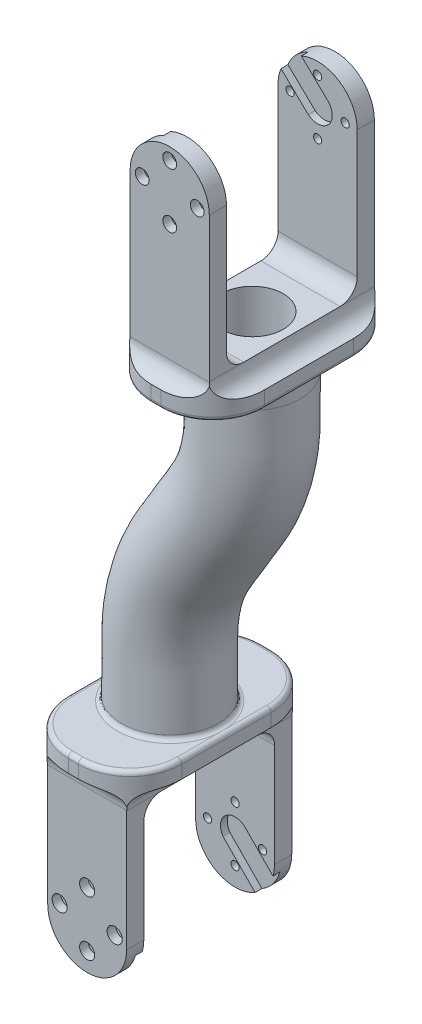
SolidWorks part; units mm, degrees
note: The reader was unsure of these and kept them because the rebuilt part matched: shared geometry of "Croquis37<4>".
material "PLA"
ref_plane "Alzado" through (0, 0, 0) normal (0, 0, 1) x (1, 0, 0)
ref_plane "Planta" through (0, 0, 0) normal (0, 1, 0) x (1, 0, 0)
ref_plane "Vista lateral" through (0, 0, 0) normal (1, 0, 0) x (0, 0, -1)
other "Centro de masa"
sketch "Croquis1" plane through (0, 0, 0) normal (0, 1, 0) x (1, 0, 0)
  circle A0 centre (0, 0) radius 14
  point P0 (0, 0)
  dimension "D1" = 28
extrude "Saliente-Extruir1" add sketch "Croquis1" along normal blind 5
sketch "Croquis2" plane through (0, 5, 0) normal (0, 1, 0) x (1, 0, 0)
  line L1 (16.5, 28) -> (-16.5, 28)
  line L2 (16.5, 28) -> (16.5, -28)
  line L3 (16.5, -28) -> (-16.5, -28)
  line L4 (-16.5, 28) -> (-16.5, -28)
  line L5 (16.5, 28) -> (-16.5, -28) construction
  line L6 (16.5, -28) -> (-16.5, 28) construction
  point P0 (0, 0)
  point P1 (0, 0)
  point P2 (0, 0)
  dimension "D1" = 33
  dimension "D2" = 56
extrude "Saliente-Extruir2" add sketch "Croquis2" along normal blind 5
sketch "Croquis5" plane through (0, 10, 0) normal (0, 1, 0) x (1, 0, 0)
  line L1 (-11.5, 24) -> (11.5, 24)
  line L2 (-11.5, 24) -> (-11.5, -24)
  line L3 (-11.5, -24) -> (11.5, -24)
  line L4 (11.5, 24) -> (11.5, -24)
  line L5 (-11.5, 24) -> (11.5, -24) construction
  line L6 (-11.5, -24) -> (11.5, 24) construction
  point P0 (0, 0)
  dimension "D1" = 48
  dimension "D2" = 23
extrude "Saliente-Extruir5" add sketch "Croquis5" along normal blind 5
sketch "Croquis10" plane through (0, 15, 0) normal (0, 1, 0) x (1, 0, 0)
  line L0 (11.5, -24) -> (11.5, 24) construction
  line L1 (-11.5, 24) -> (11.5, 24)
  line L2 (-11.5, 24) -> (-11.5, 19)
  line L3 (-11.5, 19) -> (11.5, 19)
  line L4 (11.5, 24) -> (11.5, 19)
  dimension "D1" = 5
extrude "Saliente-Extruir9" add sketch "Croquis10" along normal blind 42
sketch "Croquis11" plane through (0, 0, -24) normal (0, 0, -1) x (-1, 0, 0)
  line L0 (-11.5, 57) -> (11.5, 57) construction
  line L1 (-11.5, 57) -> (11.5, 57)
  arc A0 (11.5, 57) -> (-11.5, 57) centre (0, 57) ccw
extrude "Saliente-Extruir10" add sketch "Croquis11" against normal blind 5
sketch "Croquis13" plane through (0, 0, -19) normal (0, 0, 1) x (1, 0, 0)
  line L0 (-9.1006, 57) -> (9.153, 57) construction
  line L1 (0, 65.2781) -> (0, 47.2436) construction
  circle A0 centre (0, 57) radius 8
  circle A1 centre (0, 57) radius 4
  dimension "D1" = 16
  dimension "D2" = 8
hole_wizard "Taladro de margen para M21" positions "Croquis3D1" profile "Croquis15" hole size "M2" standard "ISO" end condition through all
sketch3d "Croquis3D1"
  line L0 (-9.1006, 57, -19) -> (9.153, 57, -19) construction
  line L1 (0, 65.2781, -19) -> (0, 47.2436, -19) construction
  circle A0 centre (0, 57, -19) radius 8 construction
  point P0 (-8, 57, -19)
  point P4 (0, 57, -11)
  point P7 (0, 65, -19)
  point P11 (8, 57, -19)
  point P12 (0, 49, -19)
sketch "Croquis15" plane through (-8, 57, -19) normal (1, 0, 0) x (0, -1, 0)
  line L0 (0, 0) -> (0, 9)
  line L1 (0, 9) -> (1.2, 9)
  line L2 (1.2, 9) -> (1.2, 0)
  line L5 (1.2, 0) -> (0, 0)
  line L11 (0, -6.35) -> (0, 107.95) construction
  dimension "Diámetro de taladro hasta el siguiente" = 2.4
  dimension "Profundidad de taladro hasta el siguiente" = 9
mirror "Simetría2" about plane through (0, 0, 0) normal (0, 0, 1) of "Taladro de margen para M21", "Saliente-Extruir9", "Saliente-Extruir10"
sketch "Croquis35" plane through (0, 0, 24) normal (0, 0, 1) x (1, 0, 0)
  circle A0 centre (0, 49) radius 2
  circle A1 centre (-8, 57) radius 2
  circle A2 centre (0, 65) radius 2
  circle A3 centre (8, 57) radius 2
  dimension "D1" = 4
  dimension "D2" = 4
  dimension "D3" = 4
  dimension "D4" = 4
extrude "Cortar-Extruir2" cut sketch "Croquis35" against normal blind 2.5
sketch "Croquis36" plane through (0, 0, 0) normal (0, -1, 0) x (1, 0, 0)
  circle A0 centre (0, 0) radius 14
  dimension "D1" = 28
sketch "Croquis37" plane through (0, 0, 0) normal (0, 0, 1) x (1, 0, 0)
  line L0 (0, 0) -> (0, -11.1508)
  line L1 (-7.1254, -36.8756) -> (-16.8746, -53.1244)
  line L2 (-24, -78.8492) -> (-24, -95)
  arc A0 (-16.8746, -53.1244) -> (-24, -78.8492) centre (26, -78.8492) ccw
  arc A1 (0, -11.1508) -> (-7.1254, -36.8756) centre (-50, -11.1508) cw
  point P7 (-24, -65)
  point P10 (0, -25)
  dimension "D5" = 50
  dimension "D1" = 25
  dimension "D2" = 30
  dimension "D3" = 24
  dimension "D4" = 95
sweep "Barrer1" add profiles "Croquis36" path "Croquis37"
sketch "Croquis39" plane through (0, -95, 0) normal (0, -1, 0) x (1, 0, 0)
  line L1 (-40.5, 28) -> (-7.5, 28)
  line L2 (-40.5, 28) -> (-40.5, -28)
  line L3 (-40.5, -28) -> (-7.5, -28)
  line L4 (-7.5, 28) -> (-7.5, -28)
  line L5 (-40.5, 28) -> (-7.5, -28) construction
  line L6 (-40.5, -28) -> (-7.5, 28) construction
  circle A1 centre (-24, 0) radius 14
  circle A2 centre (-24, 0) radius 14
  dimension "D2" = 33
  dimension "D3" = 56
  dimension "D1" = 0
extrude "Saliente-Extruir11" add sketch "Croquis39" along normal blind 5 separate body
sketch "Croquis40" plane through (0, -100, 0) normal (0, -1, 0) x (1, 0, 0)
  circle A0 centre (-24, 0) radius 14
  dimension "D1" = 28
extrude "Saliente-Extruir12" add sketch "Croquis40" against normal blind 5
sketch "Croquis42" plane through (0, -100, 0) normal (0, -1, 0) x (1, 0, 0)
  line L0 (-40.5, 0) -> (-7.5, 0) construction
  line L1 (-40.5, 28) -> (-40.5, -28) construction
  line L2 (-7.5, -28) -> (-7.5, 28) construction
  line L3 (-24, 28) -> (-24, -28) construction
  line L4 (-7.5, 28) -> (-40.5, 28) construction
  line L5 (-40.5, -28) -> (-7.5, -28) construction
  line L7 (-35.5, 24) -> (-12.5, 24)
  line L8 (-35.5, 24) -> (-35.5, -24)
  line L9 (-35.5, -24) -> (-12.5, -24)
  line L10 (-12.5, 24) -> (-12.5, -24)
  line L11 (-35.5, 24) -> (-12.5, -24) construction
  line L12 (-35.5, -24) -> (-12.5, 24) construction
  point P12 (-24, 0)
  dimension "D1" = 48
  dimension "D2" = 23
extrude "Saliente-Extruir13" add sketch "Croquis42" along normal blind 5
sketch "Croquis43" plane through (0, -105, 0) normal (0, -1, 0) x (1, 0, 0)
  line L6 (-12.5, -24) -> (-12.5, 24) construction
  line L7 (-35.5, 24) -> (-12.5, 24)
  line L8 (-35.5, 24) -> (-35.5, 19)
  line L9 (-35.5, 19) -> (-12.5, 19)
  line L10 (-12.5, 24) -> (-12.5, 19)
  dimension "D1" = 5
extrude "Saliente-Extruir14" add sketch "Croquis43" along normal blind 35
sketch "Croquis44" plane through (0, 0, 24) normal (0, 0, 1) x (1, 0, 0)
  line L1 (-35.5, -140) -> (-12.5, -140)
  line L2 (-35.5, -140) -> (-12.5, -140)
  arc A1 (-35.4609, -140) -> (-12.5391, -140) centre (-24, -140) ccw
extrude "Saliente-Extruir18" add sketch "Croquis44" against normal blind 5 contours L2 A1
mirror "Simetría6" about plane through (0, 0, 0) normal (0, 0, 1) of "Saliente-Extruir14"
sketch "Croquis55" plane through (0, 0, 24) normal (0, 0, 1) x (1, 0, 0)
  circle A0 centre (-24, -130) radius 2
  circle A1 centre (-16, -138) radius 2
  circle A2 centre (-24, -146) radius 2
  circle A3 centre (-32, -138) radius 2
  point P12 (-24, -138)
  dimension "D1" = 4
  dimension "D2" = 4
sketch "Croquis61" plane through (0, -100, 0) normal (0, -1, 0) x (1, 0, 0)
  circle A0 centre (-24, 0) radius 14
  dimension "D1" = 28
extrude "Saliente-Extruir16" add sketch "Croquis61" against normal blind 5
sketch "Croquis62" plane through (0, -95, 0) normal (0, 1, 0) x (1, 0, 0)
  circle A0 centre (-24, 0) radius 14
  dimension "D1" = 28
extrude "Saliente-Extruir17" add sketch "Croquis62" along normal blind 1
fillet "Redondeo5" radius 15 4 edges at (16.5, 7.5, -28) (-16.5, 7.5, -28) (-16.5, 7.5, 28) (16.5, 7.5, 28)
fillet "Redondeo6" radius 1.25 9 edges at (-12.1066, 5, -23.6066) (-16.5, 5, 0) (-12.1066, 5, 23.6066) (0, 5, 28) (12.1066, 5, 23.6066) (16.5, 5, 0) (12.1066, 5, -23.6066) (0, 5, -28) (0, 5, 14)
fillet "Redondeo7" radius 5 2 edges at (-11.5, 10, 0) (11.5, 10, 0)
fillet "Redondeo8" radius 5 2 edges at (0, 10, -24) (0, 10, 24)
fillet "Redondeo9" radius 5 2 edges at (0, 15, -19) (0, 15, 19)
fillet "Redondeo10" radius 15 4 edges at (-40.5, -97.5, -28) (-40.5, -97.5, 28) (-7.5, -97.5, -28) (-7.5, -97.5, 28)
fillet "Redondeo11" radius 1.25 9 edges at (-24, -95, -14) (-11.8934, -95, -23.6066) (-7.5, -95, 0) (-11.8934, -95, 23.6066) (-24, -95, 28) (-36.1066, -95, 23.6066) (-40.5, -95, 0) (-36.1066, -95, -23.6066) (-24, -95, -28)
fillet "Redondeo12" radius 5 2 edges at (-12.5, -100, 0) (-35.5, -100, 0)
fillet "Redondeo13" radius 5 2 edges at (-24, -100, -24) (-24, -100, 24)
fillet "Redondeo14" radius 5 2 edges at (-24, -105, 19) (-24, -105, -19)
sketch "Croquis67" plane through (0, -95, 0) normal (0, 1, 0) x (1, 0, 0)
  circle A0 centre (-24, 0) radius 9
  dimension "D1" = 18
sweep "Cortar-Barrer2" cut profiles "Croquis67" path "Croquis37<4>"
sketch "Croquis37<4>" plane through (0, 0, 0) normal (0, 0, 1) x (1, 0, 0) same geometry as "Croquis37"
sketch "Croquis68" plane through (0, -105, 0) normal (0, -1, 0) x (1, 0, 0)
  circle A0 centre (-24, 0) radius 9
extrude "Cortar-Extruir4" cut sketch "Croquis68" against normal blind 15
sketch "Croquis72" plane through (0, 0, 0) normal (0, -1, 0) x (1, 0, 0)
  circle A0 centre (0, 0) radius 9
extrude "Cortar-Extruir10" cut sketch "Croquis72" against normal blind 15
hole_wizard "Refrentado para tornillo con cabeza plana de M21" positions "Croquis3D2" profile "Croquis74" counterbore size "M2" standard "ISO" end condition through all
sketch3d "Croquis3D2"
  point P0 (-24, -130, 24)
  point P3 (-16, -138, 24)
  point P6 (-32, -138, 24)
  point P9 (-24, -146, 24)
sketch "Croquis74" plane through (-24, -130, 24) normal (1, 0, 0) x (0, -1, 0)
  line L0 (0, 0) -> (0, 52)
  line L1 (0, 52) -> (1.2, 52)
  line L3 (1.2, 52) -> (1.2, 2.5)
  line L4 (1.2, 2.5) -> (2.2, 2.5)
  line L5 (2.2, 2.5) -> (2.2, 0)
  line L7 (2.2, 0) -> (0, 0)
  line L11 (0, -6.35) -> (0, 107.95) construction
  dimension "Diámetro de taladro hasta el siguiente" = 2.4
  dimension "Profundidad de taladro hasta el siguiente" = 52
  dimension "Diámetro de refrentado" = 4.4
  dimension "Profundidad de refrentado" = 2.5
sketch "Croquis75" plane through (0, 0, 19) normal (0, 0, -1) x (-1, 0, 0)
  line L0 (12.9761, -143.1344) -> (21.0481, -134.9424)
  line L1 (18.1786, -149.8723) -> (27.4965, -140.416)
  arc A0 (27.4965, -140.416) -> (21.0481, -134.9424) centre (24, -138) ccw
  arc A1 (12.9761, -143.1344) -> (18.1786, -149.8723) centre (21.0576, -142.2719) ccw
  arc A3 (12.5391, -140) -> (35.4609, -140) centre (24, -140) ccw construction
  dimension "D1" = 8.5
extrude "Cortar-Extruir11" cut sketch "Croquis75" against normal blind 2
sketch "Croquis76" plane through (0, 0, 19) normal (0, 0, -1) x (-1, 0, 0)
  line L0 (4.7452, 67.4754) -> (-2.9492, 60.0602)
  line L1 (10.643, 61.3562) -> (2.6968, 53.7152)
  arc A0 (-2.9492, 60.0602) -> (3.1767, 54.1767) centre (0, 57) ccw
  arc A1 (4.7452, 67.4754) -> (10.643, 61.3562) centre (0, 57) cw
  arc A2 (11.5, 57) -> (-11.5, 57) centre (0, 57) ccw construction
  arc M12 (11.5, 57) -> (-11.5, 57) centre (0, 57) ccw
  dimension "D1" = 8.5
extrude "Cortar-Extruir12" cut sketch "Croquis76" against normal blind 2 contours L0 A0 L1 M12
mirror "Simetría7" about plane through (0, 0, 0) normal (0, 0, 1) of "Cortar-Extruir12", "Cortar-Extruir11", "Saliente-Extruir18", "Refrentado para tornillo con cabeza plana de M21", "Cortar-Extruir2"
sketch "Croquis77" plane through (0, 0, 0) normal (0, 0, 1) x (1, 0, 0)
  point P7 (-24, -138)
